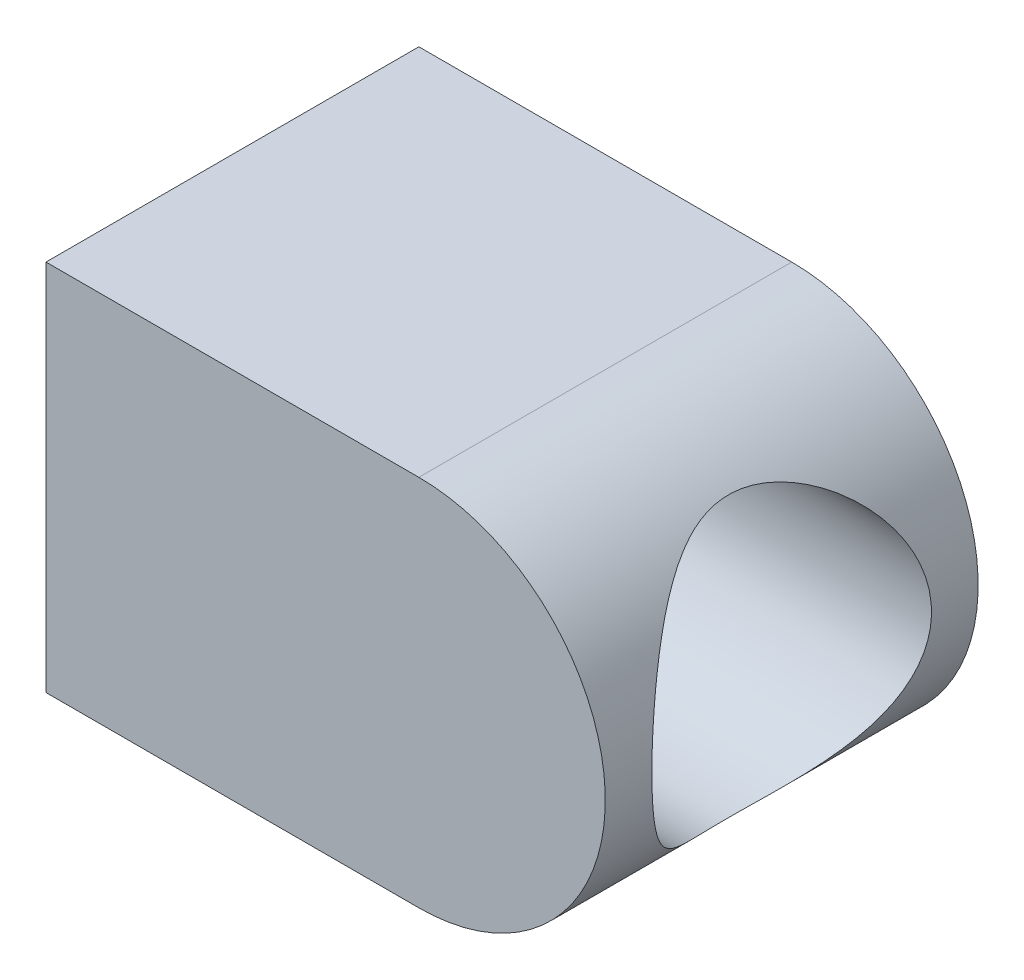
SolidWorks part; units mm, degrees
ref_plane "Front Plane" through (0, 0, 0) normal (0, 0, 1) x (1, 0, 0)
ref_plane "Top Plane" through (0, 0, 0) normal (0, 1, 0) x (1, 0, 0)
ref_plane "Right Plane" through (0, 0, 0) normal (1, 0, 0) x (0, 0, -1)
sketch "Sketch1" plane through (0, 0, 0) normal (1, 0, 0) x (0, 0, -1)
  line L1 (10, -10) -> (-10, -10)
  line L2 (10, -10) -> (10, 10)
  line L3 (10, 10) -> (-10, 10)
  line L4 (-10, -10) -> (-10, 10)
  line L5 (10, -10) -> (-10, 10) construction
  line L6 (10, 10) -> (-10, -10) construction
  point P0 (0, 0)
  dimension "D1" = 20
  dimension "D2" = 20
extrude "Boss-Extrude1" add sketch "Sketch1" along normal blind 30
fillet "Fillet3" 2 edges at (30, 10, 0) (30, -10, 0) type full round first side face at (15, 10, 0) second side face at (15, -10, 0) middle face at (30, 0, 0)
sketch "Sketch2" plane through (0, 0, 0) normal (-1, 0, 0) x (0, 0, 1)
  circle A0 centre (0, 0) radius 7.5
extrude "Cut-Extrude1" cut sketch "Sketch2" against normal blind 30
